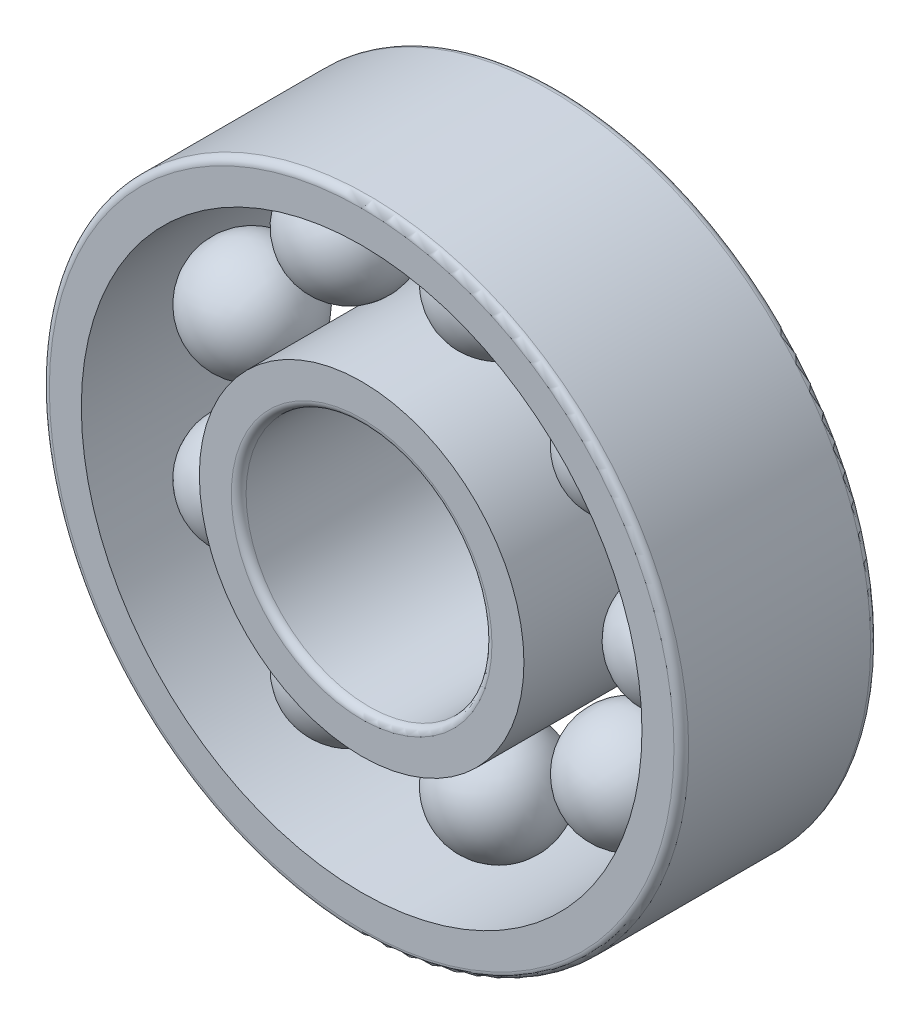
SolidWorks part; units mm, degrees
ref_plane "Front Plane" through (0, 0, 0) normal (0, 0, 1) x (1, 0, 0)
ref_plane "Top Plane" through (0, 0, 0) normal (0, 1, 0) x (1, 0, 0)
ref_plane "Right Plane" through (0, 0, 0) normal (1, 0, 0) x (0, 0, -1)
sketch "S" plane through (0, 0, 0) normal (0, 0, 1) x (1, 0, 0)
  line L0 (-4, 0) -> (4, 0) construction
  circle A0 centre (0, 0) radius 5 construction
  circle A1 centre (0, 0) radius 13 construction
  circle A2 centre (0, 0) radius 6.6 construction
  circle A3 centre (0, 0) radius 11.4 construction
  dimension "ID" = 10
  dimension "OD" = 26
  dimension "IDa" = 13.2
  dimension "ODa" = 22.8
  dimension "B" = 8
ref_axis "Z" through (0, 0, -4.4) along (0, 0, 1)
sketch "InnerS" plane through (0, 0, 0) normal (0, 1, 0) x (1, 0, 0)
  line L0 (5, -4) -> (6.6, -4)
  line L1 (6.6, -4) -> (6.6, 4)
  line L2 (6.6, 4) -> (5, 4)
  line L3 (5, 4) -> (5, -4)
  line L4 (0, -7) -> (0, 7) construction
  dimension "r1" = 5
  dimension "r2" = 6.6
  dimension "z1" = 4
  dimension "z2" = 4
revolve "InnerRing" add sketch "InnerS" angle 360 about L4
sketch "OuterS" plane through (0, 0, 0) normal (0, 1, 0) x (1, 0, 0)
  line L0 (11.4, -4) -> (13, -4)
  line L1 (13, -4) -> (13, 4)
  line L2 (13, 4) -> (11.4, 4)
  line L3 (11.4, 4) -> (11.4, -4)
  line L4 (0, -7) -> (0, 7) construction
  dimension "r1" = 11.4
  dimension "r2" = 13
  dimension "z1" = 4
  dimension "z2" = 4
revolve "OuterRing" add sketch "OuterS" angle 360 about L4
sketch "BallS" plane through (0, 0, 0) normal (0, 1, 0) x (1, 0, 0)
  line L0 (6.72, 0) -> (11.28, 0)
  arc A0 (6.72, 0) -> (11.28, 0) centre (9, 0) ccw
  dimension "r" = 2.28
  dimension "p" = 9
revolve "Ball" add sketch "BallS" angle 360 about L0
pattern_circular "BallsPattern" count 9 over 360 about axis through (0, 0, -4.4) along (0, 0, 1) of bodies 103
fillet "F1" radius 0.3 2 edges at (13, 0, -4) (13, 0, 4)
fillet "F2" radius 0.3 2 edges at (5, 0, -4) (5, 0, 4)
equation "\"r1@InnerS\" = abs(0.5*\"ID@S\")"
equation "\"r2@InnerS\" = abs(0.5*\"IDa@S\")"
equation "\"z1@InnerS\" = abs(-0.5*\"B@S\")"
equation "\"z2@InnerS\" = abs(0.5*\"B@S\")"
equation "\"r1@OuterS\" = abs(0.5*\"ODa@S\")"
equation "\"r2@OuterS\" = abs(0.5*\"OD@S\")"
equation "\"z1@OuterS\" = abs(-0.5*\"B@S\")"
equation "\"z2@OuterS\" = abs(0.5*\"B@S\")"
equation "\"r@BallS\" = abs(0.2375*\"ODa@S\"-0.2375*\"IDa@S\")"
equation "\"p@BallS\" = abs(0.25*\"IDa@S\"+0.25*\"ODa@S\")"
equation "\"N@BallsPattern\" = int(2.417*(0.25*\"IDa@S\"+0.25*\"ODa@S\")/(0.2375*\"ODa@S\"-0.2375*\"IDa@S\"))"
equation "\"r_min@F2\" = \"r_min@F1\""
